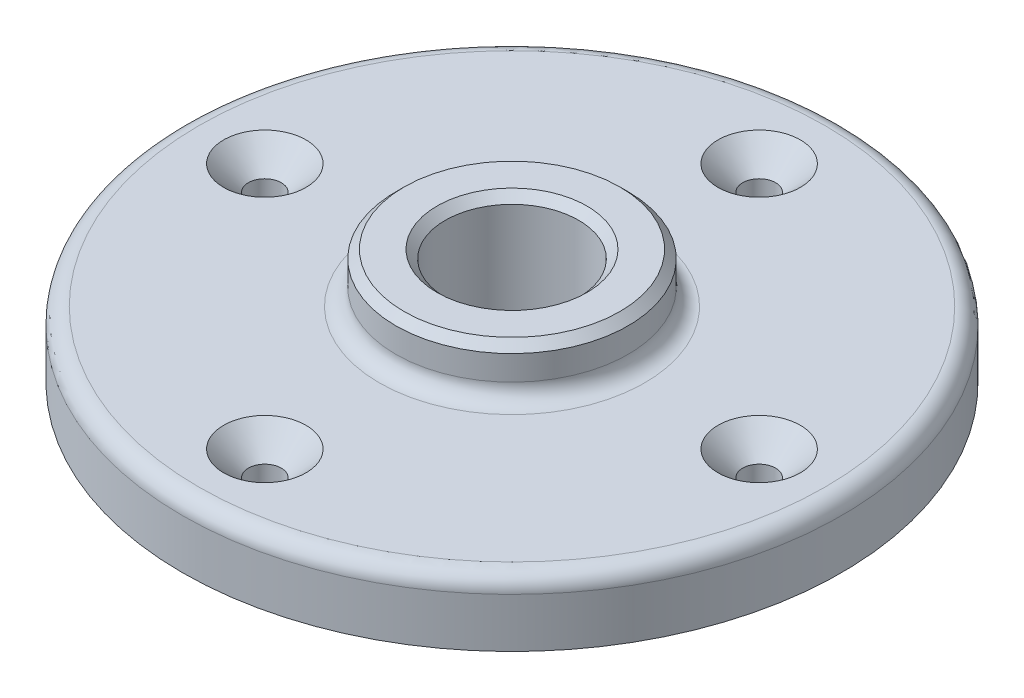
SolidWorks part; units mm, degrees
material "Nickel"
ref_plane "Front Plane" through (0, 0, 0) normal (0, 0, 1) x (1, 0, 0)
ref_plane "Top Plane" through (0, 0, 0) normal (0, 1, 0) x (1, 0, 0)
ref_plane "Right Plane" through (0, 0, 0) normal (1, 0, 0) x (0, 0, -1)
sketch "Sketch1" plane through (0, 0, 0) normal (0, 1, 0) x (1, 0, 0)
  circle A0 centre (0, 0) radius 20
  dimension "D1" = 40
extrude "Boss-Extrude1" add sketch "Sketch1" along normal blind 4
sketch "Sketch2" plane through (0, 4, 0) normal (0, 1, 0) x (1, 0, 0)
  circle A0 centre (0, 0) radius 4.05
  dimension "D1" = 8.1
extrude "Cut-Extrude1" cut sketch "Sketch2" against normal through all
sketch "Sketch3" plane through (0, 4, 0) normal (0, 1, 0) x (1, 0, 0)
  line L0 (0, 20) -> (0, 0) construction
  circle A0 centre (0, 0) radius 20 construction
  circle A1 centre (0, 15) radius 1
  dimension "D2" = 2
  dimension "D1" = 15
extrude "Cut-Extrude2" cut sketch "Sketch3" against normal through all
chamfer "Chamfer1" distance 1.5 angle 45 1 edges at (0, 4, -14)
ref_axis "Axis1" through (0, 0, 0) along (0, 1, 0)
pattern_circular "CirPattern1" count 4 over 360 about axis through (0, 0, 0) along (0, 1, 0) of "Cut-Extrude2", "Chamfer1"
fillet "Fillet1" radius 1 1 edges at (0, 4, 20)
sketch "Sketch4" plane through (0, 4, 0) normal (0, 1, 0) x (1, 0, 0)
  circle A0 centre (0, 0) radius 4.05 construction
  circle A1 centre (0, 0) radius 4.05
  circle A2 centre (0, 0) radius 7.05
  dimension "D1" = 3
extrude "Boss-Extrude2" add sketch "Sketch4" along normal blind 3
chamfer "Chamfer2" distance 0.5 angle 45 1 edges at (0, 7, 4.05)
fillet "Fillet2" radius 1 1 edges at (0, 4, 7.05)
chamfer "Chamfer3" distance 0.5 angle 45 1 edges at (0, 7, 7.05)
